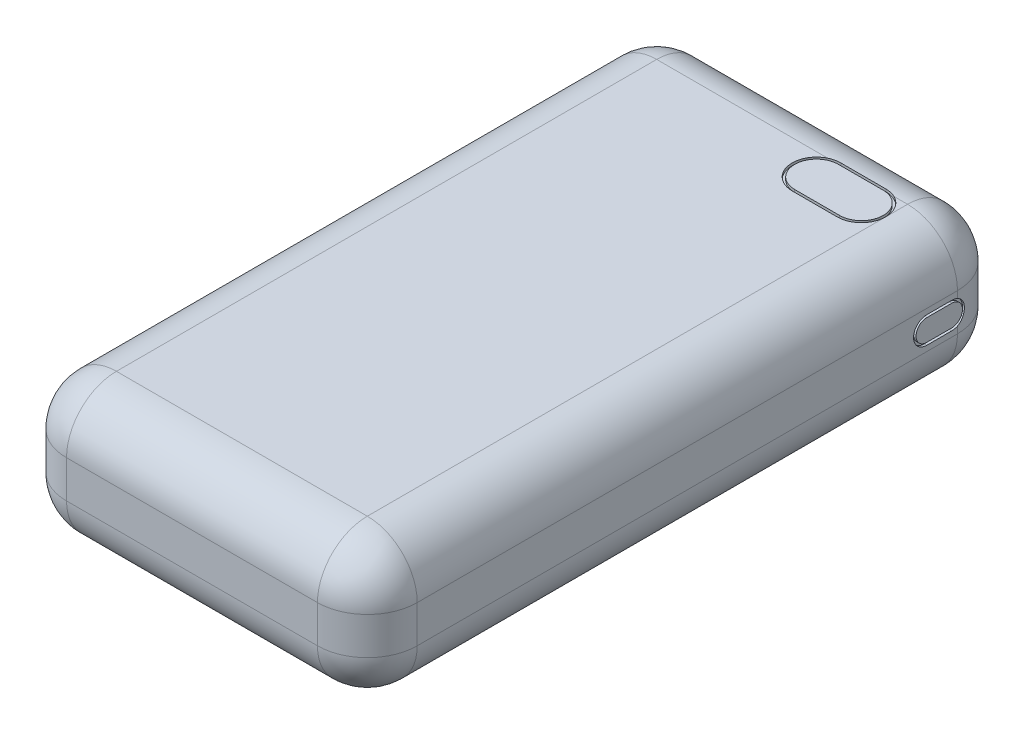
SolidWorks part; units mm, degrees
ref_plane "Front Plane" through (0, 0, 0) normal (0, 0, 1) x (1, 0, 0)
ref_plane "Top Plane" through (0, 0, 0) normal (0, 1, 0) x (1, 0, 0)
ref_plane "Right Plane" through (0, 0, 0) normal (1, 0, 0) x (0, 0, -1)
sketch "Sketch1" plane through (0, 0, 0) normal (0, 1, 0) x (1, 0, 0)
  line L1 (-35.15, 64.15) -> (35.15, 64.15)
  line L2 (-35.15, 64.15) -> (-35.15, -64.15)
  line L3 (-35.15, -64.15) -> (35.15, -64.15)
  line L4 (35.15, 64.15) -> (35.15, -64.15)
  line L5 (-35.15, 64.15) -> (35.15, -64.15) construction
  line L6 (-35.15, -64.15) -> (35.15, 64.15) construction
  point P0 (0, 0)
  dimension "D1" = 70.3
  dimension "D2" = 128.3
extrude "Boss-Extrude1" add sketch "Sketch1" along normal blind 27.5
fillet "Fillet1" radius 10 8 edges at (0, 0, -64.15) (-35.15, 0, 0) (0, 0, 64.15) (35.15, 0, 0) (0, 27.5, 64.15) (-35.15, 27.5, 0) (0, 27.5, -64.15) (35.15, 27.5, 0)
sketch "Sketch2" plane through (0, 0, 0) normal (1, 0, 0) x (0, 0, -1)
  line L0 (48, 13.75) -> (53, 13.75) construction
  line L1 (48, 15.9) -> (53, 15.9)
  line L2 (48, 11.6) -> (53, 11.6)
  line L3 (64.15, 17.5) -> (64.15, 10) construction
  line L4 (48, 16.4) -> (53, 16.4)
  line L5 (48, 11.1) -> (53, 11.1)
  arc A0 (48, 15.9) -> (48, 11.6) centre (48, 13.75) ccw
  arc A1 (53, 11.6) -> (53, 15.9) centre (53, 13.75) ccw
  arc A2 (53, 11.1) -> (53, 16.4) centre (53, 13.75) ccw
  arc A3 (48, 16.4) -> (48, 11.1) centre (48, 13.75) ccw
  point P2 (50.5, 13.75)
  point P7 (50.5, 15.9)
  point P8 (55.15, 13.75)
  point P9 (45.85, 13.75)
  point P13 (64.15, 13.75)
  dimension "D1" = 5
  dimension "D2" = 4.3
  dimension "D3" = 9
  dimension "D4" = 0.5
extrude "Cut-Extrude1" cut sketch "Sketch2" against normal blind 0.5 from surface starting at face at (35.15, 13.75, 0)
sketch "Sketch3" plane through (0, 27.5, 0) normal (0, 1, 0) x (1, 0, 0)
  line L0 (11.275, 49.775) -> (20.275, 49.775) construction
  line L1 (11.275, 54.15) -> (20.275, 54.15)
  line L2 (11.275, 45.4) -> (20.275, 45.4)
  line L3 (35.15, 64.15) -> (35.15, -64.15) construction
  line L4 (-35.15, 64.15) -> (35.15, 64.15) construction
  line L5 (11.275, 54.65) -> (20.275, 54.65)
  line L6 (11.275, 44.9) -> (20.275, 44.9)
  arc A0 (11.275, 54.15) -> (11.275, 45.4) centre (11.275, 49.775) ccw
  arc A1 (20.275, 45.4) -> (20.275, 54.15) centre (20.275, 49.775) ccw
  arc A2 (20.275, 44.9) -> (20.275, 54.65) centre (20.275, 49.775) ccw
  arc A3 (11.275, 54.65) -> (11.275, 44.9) centre (11.275, 49.775) ccw
  point P2 (15.775, 49.775)
  point P7 (15.775, 54.15)
  point P8 (24.65, 49.775)
  dimension "D1" = 9
  dimension "D2" = 8.75
  dimension "D3" = 10.5
  dimension "D4" = 10
  dimension "D5" = 0.5
extrude "Cut-Extrude2" cut sketch "Sketch3" against normal blind 0.5 from surface starting at face at (0, 27.5, 0)
fillet "Fillet2" radius 10 12 edges at (32.2211, 24.5711, 61.2211) (32.2211, 2.9289, 61.2211) (-32.2211, 24.5711, 61.2211) (-32.2211, 2.9289, 61.2211) (-32.2211, 24.5711, -61.2211) (-32.2211, 2.9289, -61.2211) (32.2211, 24.5711, -61.2211) (32.2211, 2.9289, -61.2211) (35.15, 13.75, 64.15) (-35.15, 13.75, 64.15) (-35.15, 13.75, -64.15) (35.15, 13.75, -64.15)
sketch "Sketch4" plane through (0, 0, -64.15) normal (0, 0, -1) x (-1, 0, 0)
  line L0 (-3.8, 13.75) -> (2, 13.75) construction
  line L1 (-3.8, 15.1) -> (2, 15.1)
  line L2 (-3.8, 12.4) -> (2, 12.4)
  line L3 (-25.15, 17.5) -> (-25.15, 10) construction
  line L4 (-35.15, 16.1375) -> (-35.15, 17.5) construction
  line L5 (-3.8, 15.35) -> (2, 15.35)
  line L6 (-3.8, 12.15) -> (2, 12.15)
  arc A0 (-3.8, 15.1) -> (-3.8, 12.4) centre (-3.8, 13.75) ccw
  arc A1 (2, 12.4) -> (2, 15.1) centre (2, 13.75) ccw
  arc A2 (2, 12.15) -> (2, 15.35) centre (2, 13.75) ccw
  arc A3 (-3.8, 15.35) -> (-3.8, 12.15) centre (-3.8, 13.75) ccw
  point P2 (-0.9, 13.75)
  point P7 (-25.15, 13.75)
  point P8 (-5.15, 13.75)
  point P13 (-0.9, 15.1)
  point P14 (3.35, 13.75)
  dimension "D1" = 30
  dimension "D2" = 2.7
  dimension "D3" = 8.5
  dimension "D4" = 0.25
extrude "Cut-Extrude3" cut sketch "Sketch4" against normal blind 0.25
